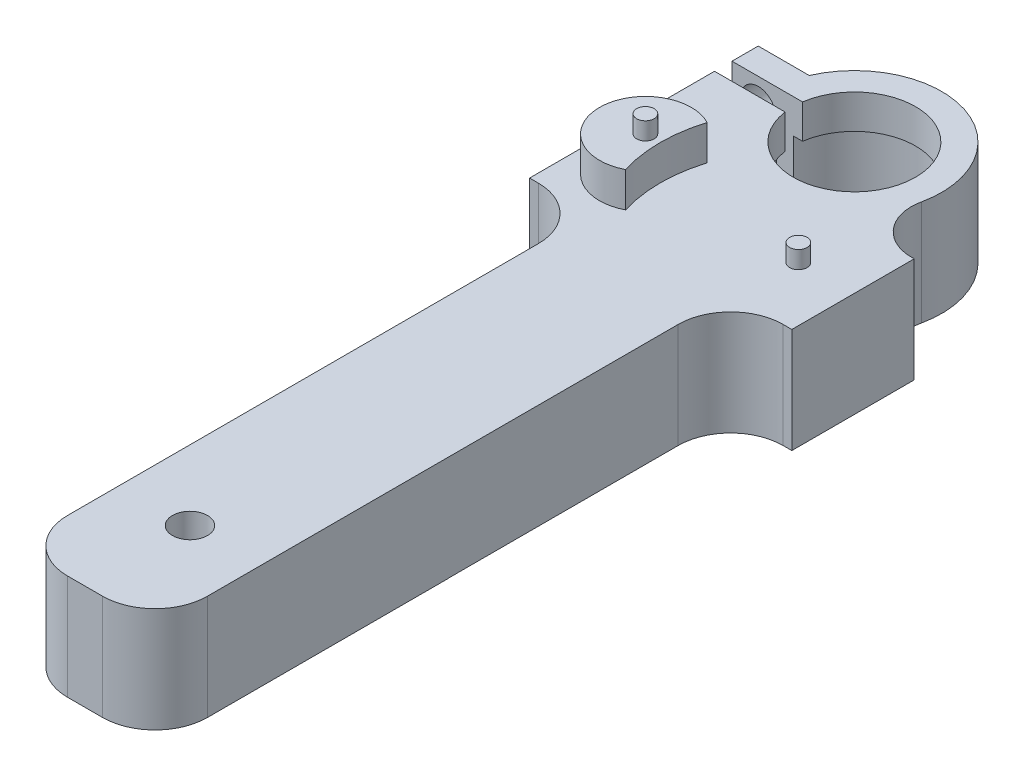
SolidWorks part; units mm, degrees
note: '?' marks a value the reader was unsure of.
material "ABS"
ref_plane "Front Plane" through (0, 0, 0) normal (0, 0, 1) x (1, 0, 0)
ref_plane "Top Plane" through (0, 0, 0) normal (0, 1, 0) x (1, 0, 0)
ref_plane "Right Plane" through (0, 0, 0) normal (1, 0, 0) x (0, 0, -1)
sketch "BaseArm" plane through (0, 0, 0) normal (0, 1, 0) x (1, 0, 0)
  line L1 (-4, 0) -> (4, 0)
  line L2 (-4, 0) -> (-4, 40)
  line L3 (-4, 40) -> (4, 40)
  line L4 (4, 0) -> (4, 40)
  dimension "D1" = 4
  dimension "D2" = 4
  dimension "D3" = 40
extrude "Boss-Extrude1" add sketch "BaseArm" along normal blind 3
sketch "Sketch2" plane through (0, 0, 0) normal (0, 1, 0) x (1, 0, 0)
  circle A2 centre (0, 44) radius 5
  circle A3 centre (0, 44) radius 4
  dimension "D1" = 8
  dimension "D2" = 10
  dimension "D3" = 44
extrude "Boss-Extrude2" add sketch "Sketch2" along normal blind 3
sketch "Sketch3" plane through (0, 0, -40) normal (0, 0, -1) x (-1, 0, 0)
  line L1 (-4, 3) -> (4, 3)
  line L2 (-4, 3) -> (-4, 0)
  line L3 (-4, 0) -> (4, 0)
  line L4 (4, 3) -> (4, 0)
extrude "Boss-Extrude3" add sketch "Sketch3" along normal up to next
ref_axis "Axis1" through (0, 3, -44) along (0, -1, 0)?
ref_plane "Plane1" through (0, 0, -44) normal (0, 0, -1) x (0, -1, 0)
sketch "Sketch5" plane through (0, 0, 0) normal (0, 1, 0) x (1, 0, 0)
  line L0 (0, -1.65) -> (0, 1.65) construction
  line L3 (-1.75, 48.4373) -> (1.75, 48.4373)
  line L4 (1.75, 52.4373) -> (1.75, 48.4373)
  line L5 (-1.75, 52.4373) -> (-1.75, 48.4373)
  line L13 (1.75, 52.4373) -> (-1.75, 52.4373)
  dimension "D2" = 3.5
extrude "Boss-Extrude6" [suppressed] add sketch "Sketch5" along normal blind 3 contours L5 L3 L4 L13
hole_wizard "Ø2.0mm Dowel Hole1" [suppressed] positions "3DSketch1" profile "Sketch7" hole size "Ø2.0" standard "ISO"
sketch3d "3DSketch1" [suppressed]
  line L0 (-1.75, 3, -52.4373) -> (-1.75, 3, -48.6837) construction
  line L1 (-1.75, 3, -52.4373) -> (-1.75, 0, -52.4373) construction
  point P0 (-1.75, 1.5, -50.9373)
  dimension "D1" = 1.5
  dimension "D2" = 1.5
sketch "Sketch7" plane through (-1.75, 1.5, -50.9373) normal (0, 1, 0) x (0, 0, 1)
  line L0 (0, 0) -> (0, 6.75)
  line L1 (0, 6.75) -> (1, 6.75)
  line L2 (1, 6.75) -> (1, 0)
  line L5 (1, 0) -> (0, 0)
  line L11 (0, -6.35) -> (0, 107.95) construction
  dimension "Thru Hole Dia." = 2
  dimension "Thru Hole Depth" = 6.75
sketch "Sketch6" plane through (0, 0, 0) normal (0, 1, 0) x (1, 0, 0)
  line L0 (0, -1.65) -> (0, 1.65) construction
  line L1 (-0.375, 47.7387) -> (0.375, 47.7387)
  line L3 (-0.375, 52.6481) -> (0.375, 52.6481)
  line L4 (0.375, 47.7387) -> (0.375, 52.6481)
  line L5 (-0.375, 47.7387) -> (-0.375, 52.6481)
  dimension "D1" = 0.75
extrude "Cut-Extrude2" [suppressed] cut sketch "Sketch6" along normal blind 5
hole_wizard "Ø2.0mm Dowel Hole2" [suppressed] positions "3DSketch2" profile "Sketch8" hole size "Ø2.0" standard "ISO"
sketch3d "3DSketch2"
  line L0 (4, 3, 0) -> (4, 0, 0) construction
  line L1 (4, 3, 0) -> (4, 3, -41) construction
  point P0 (4, 1.5, -2)
  dimension "D1" = 2
  dimension "D2" = 1.5
sketch "Sketch8" plane through (4, 1.5, -2) normal (0, 1, 0) x (0, 0, -1)
  line L0 (0, 0) -> (0, 9)
  line L1 (0, 9) -> (1, 9)
  line L2 (1, 9) -> (1, 0)
  line L5 (1, 0) -> (0, 0)
  line L11 (0, -6.35) -> (0, 107.95) construction
  dimension "Thru Hole Dia." = 2
  dimension "Thru Hole Depth" = 9
hole_wizard "Ø2.0mm Dowel Hole3" positions "3DSketch3" profile "Sketch9" hole size "Ø2.0" standard "ISO" end condition through all
sketch3d "3DSketch3"
  line L0 (-4, 3, -41) -> (-4, 3, 0) construction
  line L1 (-4, 3, 0) -> (4, 3, 0) construction
  point P0 (0, 3, -6)
  dimension "D1" = 6
  dimension "D2" = 4
sketch "Sketch9" plane through (0, 3, -6) normal (1, 0, 0) x (0, 0, 1)
  line L0 (0, 0) -> (0, 3)
  line L1 (0, 3) -> (1, 3)
  line L2 (1, 3) -> (1, 0)
  line L5 (1, 0) -> (0, 0)
  line L11 (0, -6.35) -> (0, 107.95) construction
  dimension "Thru Hole Dia." = 2
  dimension "Thru Hole Depth" = 3
sketch "Sketch10" plane through (0, 0, 0) normal (0, 1, 0) x (1, 0, 0)
  line L0 (0, -1.65) -> (0, 1.65) construction
  line L1 (0.5, 0) -> (-0.5, 0)
  line L3 (0.5, 5.9739) -> (-0.5, 5.9739)
  line L4 (-0.5, 0) -> (-0.5, 5.9739)
  line L5 (0.5, 0) -> (0.5, 5.9739)
extrude "Cut-Extrude3" [suppressed] cut sketch "Sketch10" along normal blind 5
sketch "Sketch11" plane through (0, 0, 0) normal (0, 1, 0) x (1, 0, 0)
  line L0 (-4, 41) -> (-4, 0) construction
  line L1 (-4, 9.726) -> (-3, 9.726)
  line L2 (-4, 9.726) -> (-4, 37.0294)
  line L3 (-4, 37.0294) -> (-3, 37.0294)
  line L4 (-3, 9.726) -> (-3, 37.0294)
  line L5 (0, -5.5) -> (0, 5.5) construction
  line L6 (4, 37.0294) -> (3, 37.0294)
  line L7 (3, 9.726) -> (3, 37.0294)
  line L8 (4, 9.726) -> (3, 9.726)
  line L9 (4, 9.726) -> (4, 37.0294)
  dimension "D1" = 1
extrude "Cut-Extrude4" [suppressed] cut sketch "Sketch11" along normal blind 8
fillet "Fillet1" [suppressed] radius 1
ref_point "Point1"
sketch "Sketch13" plane through (0, 3, 0) normal (0, 1, 0) x (1, 0, 0)
  line L0 (0, 44) -> (4.375, 36.4223) construction
  line L1 (4.375, 36.4223) -> (-4.375, 36.4223) construction
  line L2 (0, 44) -> (0, 36.4223) construction
  line L7 (-7.5, 32.9223) -> (7.5, 32.9223)
  line L8 (-7.5, 32.9223) -> (-7.5, 39.9223)
  line L9 (-7.5, 39.9223) -> (7.5, 39.9223)
  line L10 (7.5, 32.9223) -> (7.5, 39.9223)
  line L11 (-7.5, 32.9223) -> (7.5, 39.9223) construction
  line L12 (-7.5, 39.9223) -> (7.5, 32.9223) construction
  circle A1 centre (-4.375, 36.4223) radius 0.5
  circle A2 centre (4.375, 36.4223) radius 0.5
  point P0 (0, 36.4223)
  point P1 (0, 36.4223)
  dimension "D4" = 1
  dimension "D2" = 7
  dimension "D3" = 8.75
  dimension "D1" = 8.75
  dimension "D5" = 15
extrude "Boss-Extrude7" add sketch "Sketch13" against normal up to surface (3 mm away) up to face at (0, 0, -5)
sketch "Sketch15" plane through (0, 3, 0) normal (0, 1, 0) x (1, 0, 0)
  line L1 (-4, 39.9223) -> (-7.5, 39.9223)
  line L2 (-4, 39.9223) -> (-4, 46)
  line L3 (-4, 46) -> (-7.5, 46)
  line L4 (-7.5, 39.9223) -> (-7.5, 46)
  circle A1 centre (0, 44) radius 4 construction
  dimension "D1" = 2
extrude "Boss-Extrude8" add sketch "Sketch15" against normal up to surface (3 mm away) up to face at (0, 0, -31.7815)
sketch "Sketch20" plane through (0, 3, 0) normal (0, 1, 0) x (1, 0, 0)
  circle A0 centre (0, 44) radius 4
  circle A1 centre (0, 44) radius 3.5
  circle A2 centre (0, 44) radius 4 construction
  dimension "D1" = 7
extrude "Boss-Extrude9" add sketch "Sketch20" against normal blind 1.95
sketch "Sketch16" plane through (0, 3, 0) normal (0, 1, 0) x (1, 0, 0)
  line L0 (-7.5, 46) -> (-7.5, 32.9223) construction
  line L1 (-7.5, 44.5) -> (-3.4641, 44.5)
  line L2 (-7.5, 44.5) -> (-7.5, 43.5)
  line L3 (-7.5, 43.5) -> (-3.4641, 43.5)
  line L4 (-3.4641, 44.5) -> (-3.4641, 43.5)
  circle A0 centre (0, 44) radius 3.5 construction
  dimension "D1" = 1
extrude "Cut-Extrude5" cut sketch "Sketch16" against normal blind 3
fillet "Fillet2" [suppressed] radius 1
sketch "Sketch21" plane through (0, 0, 0) normal (0, -1, 0) x (1, 0, 0)
  circle A1 centre (-4.375, -36.4223) radius 0.5
  circle A2 centre (4.375, -36.4223) radius 0.5
extrude "Boss-Extrude10" add sketch "Sketch21" against normal blind 4
sketch "Sketch22" plane through (0, 4, 0) normal (0, 1, 0) x (1, 0, 0)
  circle A0 centre (-4.375, 36.4223) radius 0.5
  circle A1 centre (-4.375, 36.4223) radius 0.5 construction
extrude "Boss-Extrude11" add sketch "Sketch22" along normal blind 2
sketch "Sketch23" plane through (0, 3, 0) normal (0, 1, 0) x (1, 0, 0)
  arc A0 (-3.1725, 38.7557) -> (-3.1725, 34.0889) centre (-4.375, 36.4223) ccw
  arc A1 (-3.1725, 38.7557) -> (-3.1725, 34.0889) centre (4.375, 36.4223) ccw
  dimension "D1" = 15.8
extrude "Boss-Extrude12" add sketch "Sketch23" along normal blind 2
hole_wizard "M2 Tapped Hole1" positions "Sketch25" profile "Sketch27" tap size "M2" standard "ISO"
sketch "Sketch25" plane through (0, 0, -46) normal (0, 0, -1) x (-1, 0, 0)
  line L0 (7.5, 1.5) -> (6, 1.5) construction
  line L1 (7.5, 0) -> (7.5, 3) construction
  point P2 (6, 1.5)
  dimension "D1" = 1.5
sketch "Sketch27" plane through (-6, 1.5, -46) normal (1, 0, 0) x (0, 1, 0)
  line L0 (0, 0) -> (0, 10.4807)
  line L1 (0, 10.4807) -> (0.8, 10)
  line L2 (0.8, 10) -> (0.8, 0)
  line L5 (0.8, 0) -> (0, 0)
  line L10 (0, 10.4807) -> (-0.8, 10) construction
  line L11 (0, -6.35) -> (0, 107.95) construction
  dimension "Tap Drill Dia." = 1.6
  dimension "Tap Drill Depth" = 10
  dimension "Drill Angle" = 118
cosmetic thread "Hole Thread7" parameters "D1"=8, "D2"=2
sketch "Sketch28" plane through (0, 0, -46) normal (0, 0, -1) x (-1, 0, 0)
  circle A0 centre (6, 1.5) radius 1
  dimension "D1" = 2
extrude "Cut-Extrude6" cut sketch "Sketch28" against normal up to next
sketch "Sketch29" plane through (0, 0, 0) normal (0, -1, 0) x (1, 0, 0)
  line L13 (4, -41) -> (4, -39.9223)
  line L14 (4, -39.9223) -> (7.5, -39.9223)
  line L15 (7.5, -39.9223) -> (7.5, -32.9223)
  line L16 (4, -41) -> (4, -39.9223)
  line L17 (7.5, -32.9223) -> (4, -32.9223)
  line L18 (4, -32.9223) -> (4, 0)
  line L19 (4, 0) -> (-4, 0)
  line L20 (-4, 0) -> (-4, -32.9223)
  line L21 (7.5, -32.9223) -> (4, -32.9223)
  line L22 (-4, -32.9223) -> (-7.5, -32.9223)
  line L23 (-7.5, -32.9223) -> (-7.5, -43.5)
  line L24 (-7.5, -43.5) -> (-3.9686, -43.5)
  line L25 (-3.9686, -44.5) -> (-7.5, -44.5)
  line L26 (-7.5, -44.5) -> (-7.5, -46)
  line L27 (-7.5, -46) -> (-4.5826, -46)
  line L28 (4, -39.9223) -> (7.5, -39.9223)
  line L29 (7.5, -39.9223) -> (7.5, -32.9223)
  line L32 (4, -32.9223) -> (4, 0)
  line L33 (4, 0) -> (-4, 0)
  line L34 (-4, 0) -> (-4, -32.9223)
  line L37 (-7.5, -32.9223) -> (-7.5, -43.5)
  line L38 (-7.5, -43.5) -> (-3.9686, -43.5)
  line L39 (-3.9686, -44.5) -> (-7.5, -44.5)
  line L40 (-7.5, -44.5) -> (-7.5, -46)
  line L41 (-7.5, -46) -> (-4.5826, -46)
  line L42 (-4, -32.9223) -> (-7.5, -32.9223)
  circle A0 centre (0, -6) radius 1 construction
  circle A1 centre (0, -6) radius 1
  arc A18 (-3.9686, -44.5) -> (-3.9686, -43.5) centre (0, -44) ccw
  arc A19 (-4.5826, -46) -> (4, -41) centre (0, -44) ccw
  arc A29 (-3.9686, -44.5) -> (-3.9686, -43.5) centre (0, -44) ccw
  arc A30 (-4.5826, -46) -> (4, -41) centre (0, -44) ccw
  dimension "D1" = 0
extrude "Boss-Extrude13" add sketch "Sketch29" along normal blind 3
sketch "Sketch30" plane through (0, -3, 0) normal (0, -1, 0) x (1, 0, 0)
  line L13 (7.5, -32.9223) -> (4, -32.9223)
  line L14 (4, -39.9223) -> (7.5, -39.9223)
  line L15 (7.5, -39.9223) -> (7.5, -32.9223)
  line L17 (-4, -32.9223) -> (-7.5, -32.9223)
  line L18 (4, -32.9223) -> (4, 0)
  line L19 (4, 0) -> (-4, 0)
  line L20 (-4, 0) -> (-4, -32.9223)
  line L22 (4, -41) -> (4, -39.9223)
  line L23 (-7.5, -32.9223) -> (-7.5, -43.5)
  line L24 (-7.5, -43.5) -> (-3.9686, -43.5)
  line L25 (-3.9686, -44.5) -> (-7.5, -44.5)
  line L26 (-7.5, -44.5) -> (-7.5, -46)
  line L27 (-7.5, -46) -> (-4.5826, -46)
  line L32 (4, -16.7819) -> (4, 0)
  line L33 (4, 0) -> (-4, 0)
  line L34 (-4, 0) -> (-4, -16.7819)
  arc A0 (-4, -16.7819) -> (4, -16.7819) centre (0, -6) ccw
  circle A1 centre (0, -6) radius 1 construction
  circle A2 centre (0, -6) radius 1
  arc A20 (-3.9686, -44.5) -> (-3.9686, -43.5) centre (0, -44) ccw
  arc A21 (-4.5826, -46) -> (4, -41) centre (0, -44) ccw
  point P3 (-3.9942, -16.7819)
  point P6 (4, -16.7682)
  point P7 (-4, -16.7682)
  point P11 (0, 0)
  point P14 (0, 0)
  point P15 (0, 0)
  point P16 (4.0042, -16.7819)
  point P17 (-4.0046, -16.7819)
  dimension "D1" = 23
  dimension "D2" = 0
extrude "Boss-Extrude14" add sketch "Sketch30" along normal blind 0.01
fillet "Fillet3" radius 3 4 edges at (-4, -0.005, 0) (4, -0.005, 0) (4, 0, -32.9223) (-4, 0, -32.9223)
sketch "Sketch31" plane through (0, 3, 0) normal (0, 1, 0) x (1, 0, 0)
  line L0 (7.3322, 39.9223) -> (4, 39.9223)
  line L2 (4, 39.9223) -> (4, 41)
  arc A0 (4.8881, 42.9482) -> (7.3322, 39.9223) centre (7.3322, 42.4223) ccw
  arc A1 (4, 41) -> (-4.5826, 46) centre (0, 44) ccw construction
  arc A2 (4, 41) -> (4.8881, 42.9482) centre (0, 44) ccw
  dimension "D1" = 5
extrude "Boss-Extrude15" add sketch "Sketch31" against normal up to surface (6 mm away) up to face at (-0.5143, -3, -36.5131)
